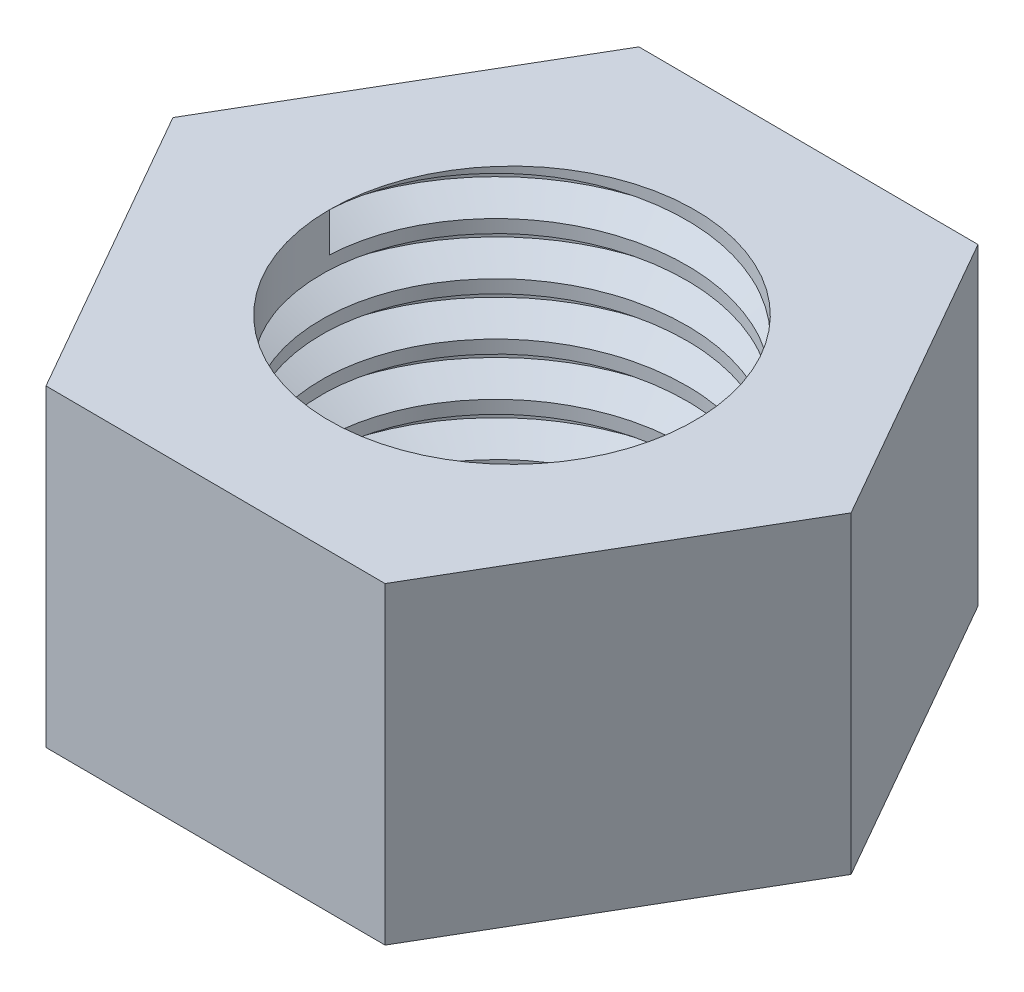
SolidWorks part; units mm, degrees
ref_plane "Front Plane" through (0, 0, 0) normal (0, 0, 1) x (1, 0, 0)
ref_plane "Top Plane" through (0, 0, 0) normal (0, 1, 0) x (1, 0, 0)
ref_plane "Right Plane" through (0, 0, 0) normal (1, 0, 0) x (0, 0, -1)
sketch "Sketch2" plane through (0, 0, 0) normal (0, 1, 0) x (1, 0, 0)
  line L1 (3.2912, 5.638) -> (-3.2371, 5.6693)
  line L2 (-3.2371, 5.6693) -> (-6.5283, 0.0313)
  line L3 (-6.5283, 0.0313) -> (-3.2912, -5.638)
  line L4 (-3.2912, -5.638) -> (3.2371, -5.6693)
  line L5 (3.2371, -5.6693) -> (6.5283, -0.0313)
  line L6 (6.5283, -0.0313) -> (3.2912, 5.638)
  circle A0 centre (0, 0) radius 3.5
  circle A1 centre (0, 0) radius 5.6537 construction
extrude "Boss-Extrude1" add sketch "Sketch2" along normal blind 6
sketch "Sketch3" plane through (0, 6, 0) normal (0, 1, 0) x (1, 0, 0)
  circle A0 centre (0, 0) radius 5.6552
thread "Thread1" pitch 1 method cut profile "Thread Profile1" start angle 0, offset 0, length 6, pitch 1, diameter 7
ref_plane "Plane1" through (-3.5, 6, 0) normal (0, 0, 1) x (-1, 0, 0)
sketch "Thread Profile1" plane through (-3.5, 6, 0) normal (0, 0, 1) x (-1, 0, 0)
  line L0 (0, 0) -> (0, 1) construction
  line L1 (0, 0) -> (0.5413, 0.3125)
  line L2 (0.5413, 0.3125) -> (0.5413, 0.4375)
  line L3 (0.5413, 0.4375) -> (0, 0.75)
  line L4 (0.5413, 0.375) -> (0, 0.375) construction
  line L11 (0, 0) -> (0, 0.75)
  point P2 (0, 0)
  dimension "Pitch" = 1
  dimension "Profile_Angle" = 60
  dimension "Profile_Land" = 0.125
  dimension "Profile_Height" = 0.5413
